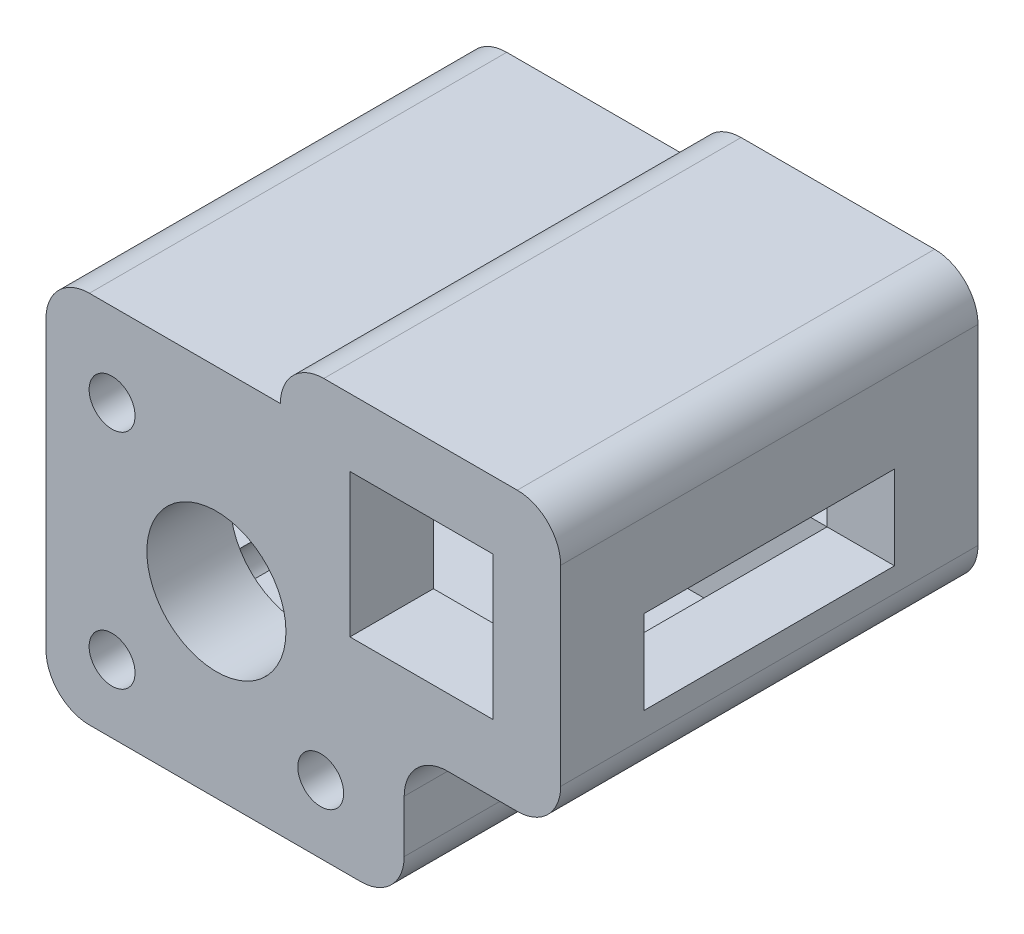
SolidWorks part; units mm, degrees
material "ABS"
ref_plane "前视基准面" through (0, 0, 0) normal (0, 0, 1) x (1, 0, 0)
ref_plane "上视基准面" through (0, 0, 0) normal (0, 1, 0) x (1, 0, 0)
ref_plane "右视基准面" through (0, 0, 0) normal (1, 0, 0) x (0, 0, -1)
sketch "草图1" plane through (0, 0, 0) normal (0, 0, 1) x (1, 0, 0)
  line L1 (-18.5, 15) -> (18.5, 15)
  line L2 (-18.5, 15) -> (-18.5, -15)
  line L3 (-18.5, -15) -> (18.5, -15)
  line L4 (18.5, 15) -> (18.5, -15)
  line L5 (-18.5, 15) -> (18.5, -15) construction
  line L6 (-18.5, -15) -> (18.5, 15) construction
  line L11 (3.5, 10) -> (13.5, 10) construction
  line L12 (3.5, 10) -> (3.5, 0) construction
  line L17 (3.5, 0) -> (13.5, 0) construction
  line L18 (13.5, 10) -> (13.5, 0) construction
  line L23 (3.5, 10) -> (13.5, 0) construction
  line L24 (3.5, 0) -> (13.5, 10) construction
  line L25 (3.35, 10.15) -> (13.65, 10.15)
  line L26 (3.35, 10.15) -> (3.35, -0.15)
  line L27 (3.35, -0.15) -> (13.65, -0.15)
  line L28 (13.65, 10.15) -> (13.65, -0.15)
  line L29 (3.35, 10.15) -> (13.65, -0.15) construction
  line L30 (3.35, -0.15) -> (13.65, 10.15) construction
  point P0 (0, 0)
  point P5 (8.5, 5)
  point P9 (8.5, 5)
  dimension "D1" = 30
  dimension "D2" = 37
  dimension "D3" = 10
  dimension "D4" = 5
  dimension "D5" = 5
  dimension "D6" = 10.3
extrude "凸台-拉伸1" add sketch "草图1" along normal blind 30
sketch "草图2" plane through (0, 0, 30) normal (0, 0, 1) x (1, 0, 0)
  line L1 (-18.5, -15) -> (18.5, -15) construction
  line L2 (-18.5, 15) -> (-18.5, -15) construction
  line L3 (-0.5, 0) -> (17.5, 0) construction
  line L4 (18.5, -15) -> (7.25, -15)
  line L5 (18.5, -15) -> (18.5, -5)
  line L6 (18.5, -5) -> (7.25, -5)
  line L7 (7.25, -15) -> (7.25, -5)
  circle A0 centre (-13.75, 5.8805) radius 1.65
  circle A1 centre (-13.75, -10.1195) radius 1.65
  circle A2 centre (1.25, -10.1195) radius 1.65
  dimension "D1" = 3.3
  dimension "D2" = 3.3
  dimension "D3" = 3.3
  dimension "D4" = 4.8805
  dimension "D5" = 4.75
  dimension "D6" = 4.75
  dimension "D7" = 16
  dimension "D8" = 4.8805
  dimension "D9" = 15
  dimension "D10" = 5
  dimension "D11" = 6
extrude "切除-拉伸1" cut sketch "草图2" against normal through all
sketch "草图3" plane through (0, 0, 30) normal (0, 0, 1) x (1, 0, 0)
  line L8 (3.35, 10.15) -> (3.35, -0.15) construction
  line L9 (-18.5, 15) -> (-1.65, 15)
  line L10 (-18.5, 15) -> (-18.5, 11.8805)
  line L11 (-18.5, 11.8805) -> (-1.65, 11.8805)
  line L12 (-1.65, 15) -> (-1.65, 11.8805)
  line L14 (-13.75, 5.8805) -> (1.25, 5.8805) construction
  line L15 (-13.75, 5.8805) -> (-13.75, -10.1195) construction
  line L16 (-13.75, -10.1195) -> (1.25, -10.1195) construction
  line L17 (1.25, 5.8805) -> (1.25, -10.1195) construction
  circle A2 centre (-13.75, 5.8805) radius 1.65 construction
  circle A3 centre (-6.25, -2.1195) radius 5
  dimension "D3" = 10
  dimension "D1" = 6
  dimension "D2" = 5
extrude "切除-拉伸2" cut sketch "草图3" against normal through all
sketch "草图4" plane through (-18.5, 0, 0) normal (-1, 0, 0) x (0, 0, 1)
  line L0 (30, -15) -> (0, -15) construction
  line L1 (24, 5.8805) -> (6, 5.8805)
  line L2 (24, 5.8805) -> (24, -9)
  line L3 (24, -9) -> (6, -9)
  line L4 (6, 5.8805) -> (6, -9)
  line L5 (24, 5.8805) -> (6, -9) construction
  line L6 (24, -9) -> (6, 5.8805) construction
  line L7 (30, 11.8805) -> (30, -15) construction
  line L8 (0, 11.8805) -> (0, -15) construction
  line L9 (0, 11.8805) -> (30, 11.8805) construction
  point P0 (15, -1.5598)
  dimension "D1" = 6
  dimension "D2" = 6
  dimension "D3" = 6
  dimension "D4" = 6
extrude "切除-拉伸3" cut sketch "草图4" against normal through all
sketch "草图5" plane through (0, 0, 6) normal (0, 0, 1) x (1, 0, 0)
  line L1 (18.5, -5) -> (13.65, -5)
  line L2 (18.5, -5) -> (18.5, -0.15)
  line L3 (18.5, -0.15) -> (13.65, -0.15)
  line L4 (13.65, -5) -> (13.65, -0.15)
extrude "凸台-拉伸2" add sketch "草图5" along normal up to surface (18 mm away) up to face at (-0.25, -1.8504, 24)
fillet "圆角2" radius 3.12 8 edges at (-1.65, 15, 15) (-18.5, 11.8805, 15) (18.5, 15, 15) (18.5, -5, 15) (7.25, -5, 3) (7.25, -5, 27) (7.25, -15, 15) (-18.5, -15, 15)
